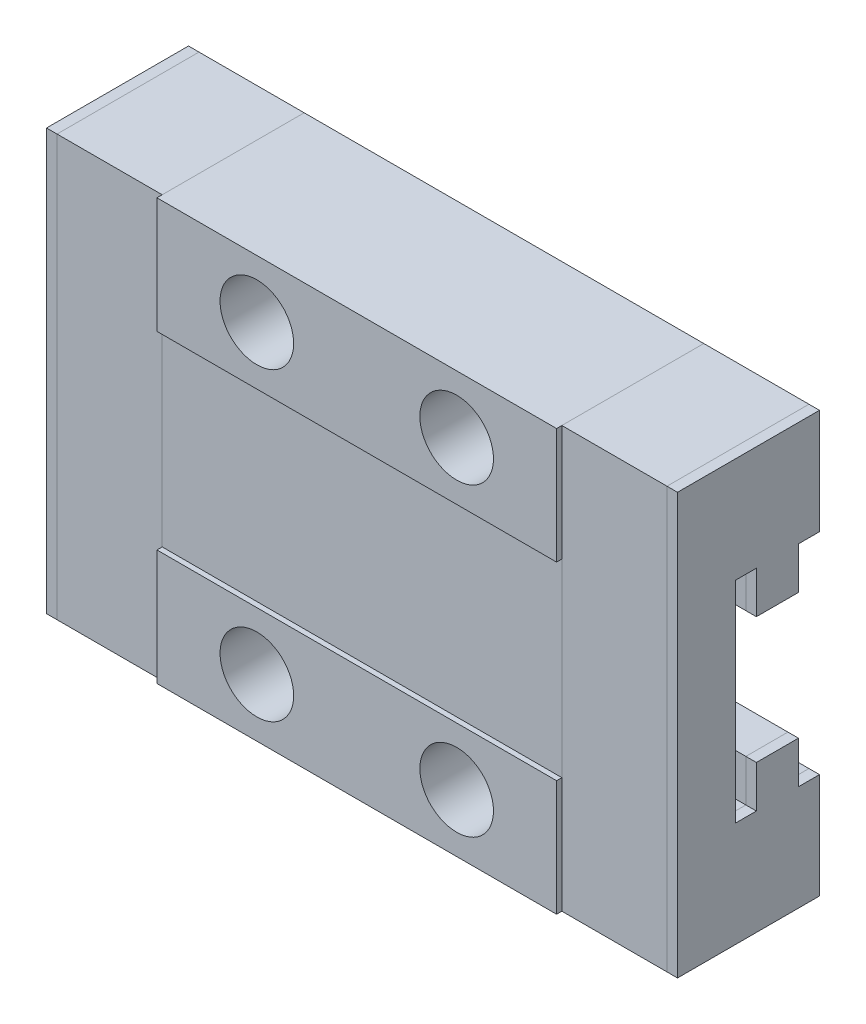
SolidWorks part; units mm, degrees
ref_plane "Plan de face" through (0, 0, 0) normal (0, 0, 1) x (1, 0, 0)
ref_plane "Plan de dessus" through (0, 0, 0) normal (0, 1, 0) x (1, 0, 0)
ref_plane "Plan de droite" through (0, 0, 0) normal (1, 0, 0) x (0, 0, -1)
sketch "Esquisse1" plane through (0, 0, 0) normal (0, 0, 1) x (1, 0, 0)
  line L0 (0, 0) -> (0, 10) construction
  line L1 (9.5, -10) -> (-9.5, -10)
  line L2 (9.5, -10) -> (9.5, 10)
  line L3 (9.5, 10) -> (-9.5, 10)
  line L4 (-9.5, -10) -> (-9.5, 10)
  line L5 (9.5, -10) -> (-9.5, 10) construction
  line L6 (9.5, 10) -> (-9.5, -10) construction
  line L7 (9.5, -4.5) -> (-9.5, -4.5)
  line L8 (9.5, -4.5) -> (9.5, 4.5)
  line L9 (9.5, 4.5) -> (-9.5, 4.5)
  line L10 (-9.5, -4.5) -> (-9.5, 4.5)
  line L11 (9.5, -4.5) -> (-9.5, 4.5) construction
  line L12 (9.5, 4.5) -> (-9.5, -4.5) construction
  line L13 (-14.5, -10) -> (-14.5, 10)
  line L14 (14.5, -10) -> (9.5, -10)
  line L15 (14.5, -10) -> (14.5, 10)
  line L16 (14.5, 10) -> (9.5, 10)
  line L17 (9.5, -10) -> (9.5, 10)
  line L18 (14.5, -10) -> (9.5, 10) construction
  line L19 (14.5, 10) -> (9.5, -10) construction
  line L20 (15, -10) -> (14.5, -10)
  line L21 (15, -10) -> (15, 10)
  line L22 (15, 10) -> (14.5, 10)
  line L23 (14.5, -10) -> (14.5, 10)
  line L24 (15, -10) -> (14.5, 10) construction
  line L25 (15, 10) -> (14.5, -10) construction
  line L26 (-15, 10) -> (-14.5, 10)
  line L27 (-15, -10) -> (-15, 10)
  line L28 (-15, -10) -> (-14.5, -10)
  line L29 (-9.5, -10) -> (-9.5, 10)
  line L30 (-14.5, 10) -> (-9.5, 10)
  line L31 (-14.5, -10) -> (-14.5, 10)
  line L32 (-14.5, -10) -> (-9.5, -10)
  line L33 (-9.5, -4.5) -> (-9.5, 4.5)
  line L34 (-9.5, -10) -> (-9.5, 10)
  line L35 (-9.5, 7.25) -> (0, 7.25) construction
  line L36 (-4.75, 4.5) -> (-4.75, 10) construction
  line L37 (0, 0) -> (-9.5, 0) construction
  circle A0 centre (-4.75, 7.25) radius 1.75
  circle A1 centre (4.75, 7.25) radius 1.75
  circle A2 centre (4.75, -7.25) radius 1.75
  circle A3 centre (-4.75, -7.25) radius 1.75
  point P0 (0, 0)
  point P5 (0, 0)
  point P13 (12, 0)
  point P14 (14.75, 0)
  point P28 (-4.75, 7.25)
  point P33 (-4.75, 7.25)
  dimension "D6" = 3.5
  dimension "D1" = 19
  dimension "D2" = 20
  dimension "D3" = 9
  dimension "D4" = 0.5
  dimension "D5" = 5
extrude "Boss.-Extru.1" add sketch "Esquisse1" along normal blind 7 contours L9 L2 L3 L4 A0 A1 | L2 L7 L4 L1 A2 A3 region at (0, -7.25, 0) region at (0, 7.25, 0)
extrude "Boss.-Extru.2" add sketch "Esquisse1<3>" along normal blind 6.75 contours L2 L9 L4 L7 region at (0, 0, 0)
sketch "Esquisse1<3>" plane through (0, 0, 0) normal (0, 0, 1) x (1, 0, 0) same geometry as "Esquisse1"
extrude "Boss.-Extru.3" add sketch "Esquisse1<4>" along normal blind 6.75 separate body contours L13 L32 L4 L30 | L15 L16 L2 L14 region at (12, 0, 0) region at (-12, 0, 0)
sketch "Esquisse1<4>" plane through (0, 0, 0) normal (0, 0, 1) x (1, 0, 0) same geometry as "Esquisse1"
extrude "Boss.-Extru.4" add sketch "Esquisse1<5>" along normal blind 6.75 separate body contours L27 L28 L13 L26 | L21 L22 L15 L20 region at (14.75, 0, 0) region at (-14.75, 0, 0)
sketch "Esquisse1<5>" plane through (0, 0, 0) normal (0, 0, 1) x (1, 0, 0) same geometry as "Esquisse1"
sketch "Esquisse2" plane through (-15, 0, 0) normal (-1, 0, 0) x (0, 0, 1)
  line L0 (0, -10) -> (0, 10) construction
  line L1 (4, -5) -> (0, -5)
  line L2 (4, -5) -> (4, 5)
  line L3 (4, 5) -> (0, 5)
  line L4 (0, -5) -> (0, 5)
  line L5 (4, -5) -> (0, 5) construction
  line L6 (4, 5) -> (0, -5) construction
  line L7 (1, 4) -> (0, 4) construction
  line L8 (3, 3) -> (1, 3)
  line L9 (3, 3) -> (3, 5)
  line L10 (3, 5) -> (1, 5)
  line L11 (1, 3) -> (1, 5)
  line L12 (3, 3) -> (1, 5) construction
  line L13 (3, 5) -> (1, 3) construction
  line L14 (3, -3) -> (1, -3)
  line L15 (3, -3) -> (3, -5)
  line L16 (3, -5) -> (1, -5)
  line L17 (1, -3) -> (1, -5)
  line L18 (3, -3) -> (1, -5) construction
  line L19 (3, -5) -> (1, -3) construction
  line L20 (3, 4) -> (4, 4) construction
  point P0 (2, 0)
  point P7 (2, -4)
  point P9 (2, 4)
  line M11 (0, 10) -> (0, -10)
  dimension "D1" = 10
  dimension "D2" = 4
  dimension "D3" = 1
  dimension "D4" = 2
extrude "Enlèv. mat.-Extru.1" cut sketch "Esquisse2" against normal up to surface (30 mm away) contours L17 L14 L15 L1 L2 L3 L9 L8 L11 M11 region at (-15, 0, 2) up to face at (15, 0, 3.375)
sketch "Esquisse4" plane through (0, 0, 0) normal (0, 0, -1) x (-1, 0, 0)
  circle A0 centre (-4.75, 7.25) radius 1.75
  circle A1 centre (4.75, 7.25) radius 1.75
  circle A2 centre (4.75, -7.25) radius 1.75
  circle A3 centre (-4.75, -7.25) radius 1.75
  circle A4 centre (-4.75, 7.25) radius 1.75 construction
  circle A5 centre (4.75, 7.25) radius 1.75 construction
  circle A6 centre (-4.75, -7.25) radius 1.75 construction
  circle A7 centre (4.75, -7.25) radius 1.75 construction
extrude "Boss.-Extru.6" add sketch "Esquisse4" against normal blind 2.5
